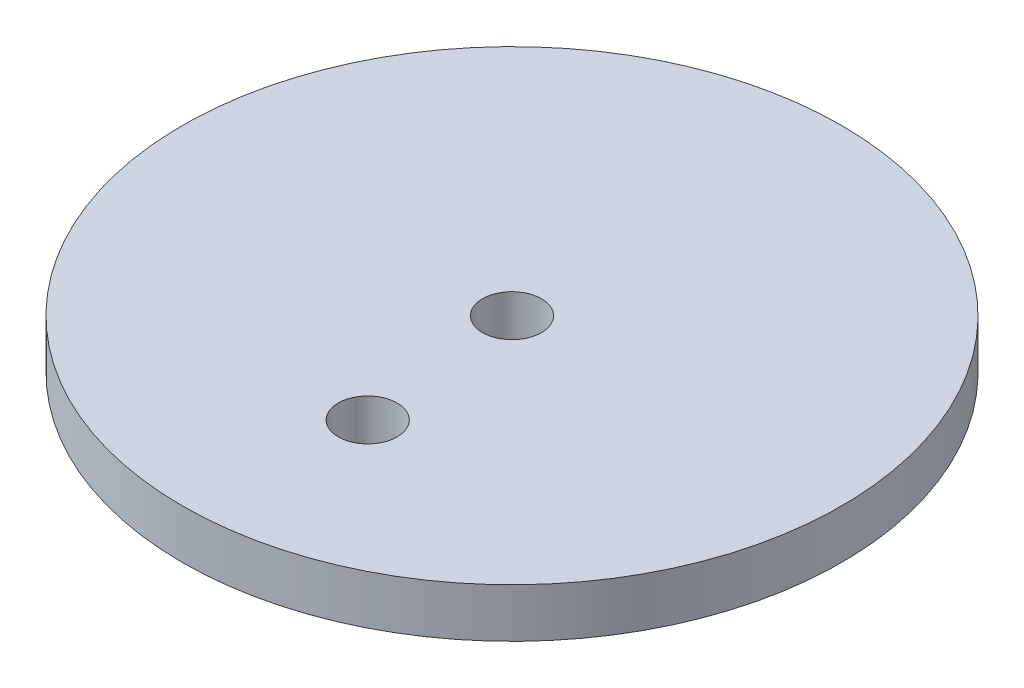
SolidWorks part; units mm, degrees
ref_plane "Front Plane" through (0, 0, 0) normal (0, 0, 1) x (1, 0, 0)
ref_plane "Top Plane" through (0, 0, 0) normal (0, 1, 0) x (1, 0, 0)
ref_plane "Right Plane" through (0, 0, 0) normal (1, 0, 0) x (0, 0, -1)
sketch "Sketch1" plane through (0, 0, 0) normal (0, 0, 1) x (1, 0, 0)
  line L0 (1.8, 9.3981) -> (1.8, 6.3981)
  line L1 (1.8, 6.3981) -> (20.1649, 6.3981)
  line L2 (20.1649, 6.3981) -> (20.1649, 9.3981)
  line L3 (20.1649, 9.3981) -> (1.8, 9.3981)
  line L4 (0, 9.3981) -> (0, 6.3981) construction
revolve "Revolve1" add sketch "Sketch1" angle 360 about L4 reverse direction yes
sketch "Sketch2" plane through (0, 9.3981, 0) normal (0, 1, 0) x (1, 0, 0)
  circle A0 centre (1.1099, -9.9382) radius 1.8
  circle A1 centre (0, 0) radius 1.8 construction
  dimension "D1" = 10
  dimension "D2" = 3.6
extrude "Cut-Extrude1" cut sketch "Sketch2" against normal blind 10
